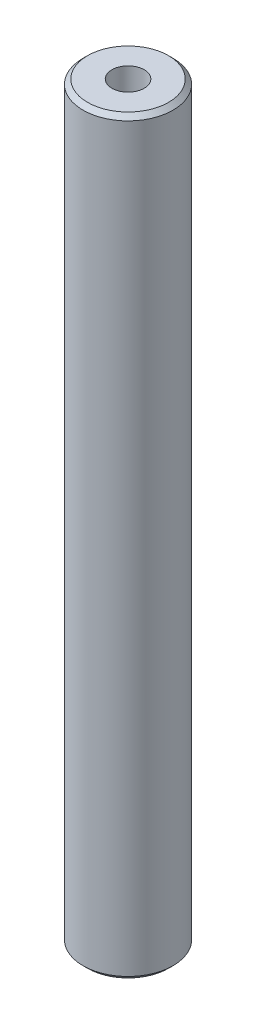
SolidWorks part; units mm, degrees
ref_plane "Front Plane" through (0, 0, 0) normal (0, 0, 1) x (1, 0, 0)
ref_plane "Top Plane" through (0, 0, 0) normal (0, 1, 0) x (1, 0, 0)
ref_plane "Right Plane" through (0, 0, 0) normal (1, 0, 0) x (0, 0, -1)
sketch "Sketch1" plane through (0, 0, 0) normal (0, 1, 0) x (1, 0, 0)
  circle A0 centre (0, 0) radius 12.5
  dimension "SHAFT_OD" = 25
extrude "Boss-Extrude1" add sketch "Sketch1" along normal blind 208.3573
sketch "Sketch2" plane through (0, 0, 0) normal (0, 1, 0) x (1, 0, 0)
  circle A0 centre (0, 0) radius 4.4797
  dimension "BORE_D" = 8.9595
extrude "Cut-Extrude1" cut sketch "Sketch2" along normal through all
chamfer "Chamfer1" distance 1.2519 angle 45 2 edges at (0, 208.3573, 12.5) (0, 0, 12.5)
